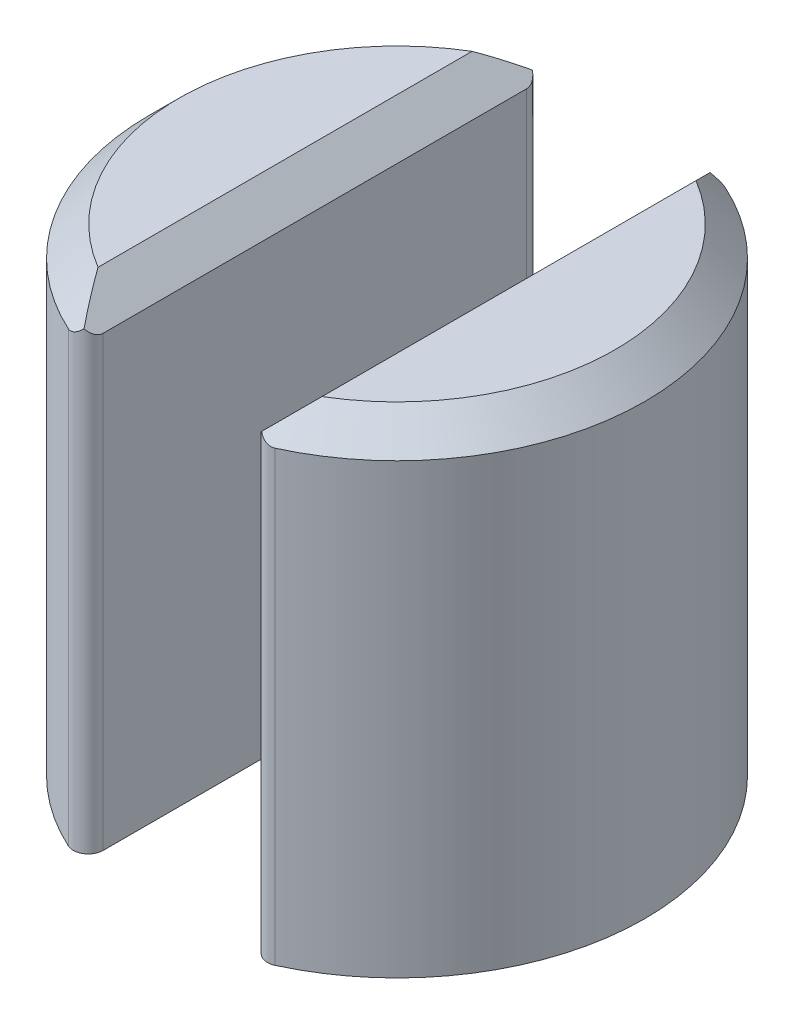
SolidWorks part; units mm, degrees
ref_plane "Front Plane" through (0, 0, 0) normal (0, 0, 1) x (1, 0, 0)
ref_plane "Top Plane" through (0, 0, 0) normal (0, 1, 0) x (1, 0, 0)
ref_plane "Right Plane" through (0, 0, 0) normal (1, 0, 0) x (0, 0, -1)
sketch "Sketch1" plane through (0, 0, 0) normal (0, 1, 0) x (1, 0, 0)
  line L0 (-1.375, 3.9156) -> (-1.375, -3.9156)
  line L1 (-1.375, 0.875) -> (1.375, 0.875)
  line L2 (-1.375, 0.875) -> (-1.375, -0.875)
  line L3 (-1.375, -0.875) -> (1.375, -0.875)
  line L4 (1.375, 0.875) -> (1.375, -0.875)
  line L5 (1.375, 3.9156) -> (1.375, -3.9156)
  circle A0 centre (0, 0) radius 4.15
  point P2 (0, 0.875)
  point P8 (-1.375, 0)
  dimension "D1" = 8.3
  dimension "D2" = 2.75
  dimension "D3" = 1.75
extrude "Boss-Extrude1" add sketch "Sketch1" along normal blind 3.75 contours L0 A0 | L5 A0 L4 | L4 L1 L0 L3 region at (-2.5246, 0, 0) region at (0, 0, 0) region at (2.5246, 0, 0)
sketch "Sketch2" plane through (0, 3.75, 0) normal (0, 1, 0) x (1, 0, 0)
  line L0 (-1.375, 0.875) -> (-1.375, -0.875)
  line L1 (1.375, -0.875) -> (1.375, 0.875)
  line L6 (-1.375, 0.875) -> (-1.375, 3.9156)
  line L7 (-1.375, -3.9156) -> (-1.375, -0.875)
  line L8 (-1.375, -0.875) -> (1.375, -0.875)
  line L9 (1.375, -0.875) -> (1.375, -3.9156)
  line L10 (1.375, 3.9156) -> (1.375, 0.875)
  line L11 (1.375, 0.875) -> (-1.375, 0.875)
  line L12 (-1.375, 0.875) -> (-1.375, 3.9156)
  line L13 (-1.375, -3.9156) -> (-1.375, -0.875)
  line L14 (-1.375, -0.875) -> (1.375, -0.875)
  line L15 (1.375, -0.875) -> (1.375, -3.9156)
  line L16 (1.375, 3.9156) -> (1.375, 0.875)
  line L17 (1.375, 0.875) -> (-1.375, 0.875)
  arc A2 (-1.375, 3.9156) -> (-1.375, -3.9156) centre (0, 0) ccw
  arc A3 (1.375, -3.9156) -> (1.375, 3.9156) centre (0, 0) ccw
  arc A4 (-1.375, 3.9156) -> (-1.375, -3.9156) centre (0, 0) ccw
  arc A5 (1.375, -3.9156) -> (1.375, 3.9156) centre (0, 0) ccw
  line M9 (-1.375, 0.875) -> (-1.375, 3.9156)
  arc M10 (-1.375, 3.9156) -> (-1.375, -3.9156) centre (0, 0) ccw
  line M11 (-1.375, -3.9156) -> (-1.375, -0.875)
  line M13 (1.375, -0.875) -> (1.375, -3.9156)
  arc M14 (1.375, -3.9156) -> (1.375, 3.9156) centre (0, 0) ccw
  line M15 (1.375, 3.9156) -> (1.375, 0.875)
  dimension "D1" = 0
extrude "Boss-Extrude2" add sketch "Sketch2" along normal blind 4.25 contours L1 M13 M14 M15 | L0 M9 M10 M11 region at (-2.5246, 3.75, 0) region at (2.5246, 3.75, 0)
fillet "Fillet1" radius 0.25 4 edges at (-1.375, 4, -3.9156) (1.375, 4, -3.9156) (-1.375, 4, 3.9156) (1.375, 4, 3.9156)
chamfer "Chamfer1" distance 0.5 angle 45 6 edges at (4.15, 8, 0) (-4.15, 8, 0) (-1.375, 8, 0) (1.375, 8, 0) (0, 3.75, 0.875) (0, 3.75, -0.875) tangent propagation no
